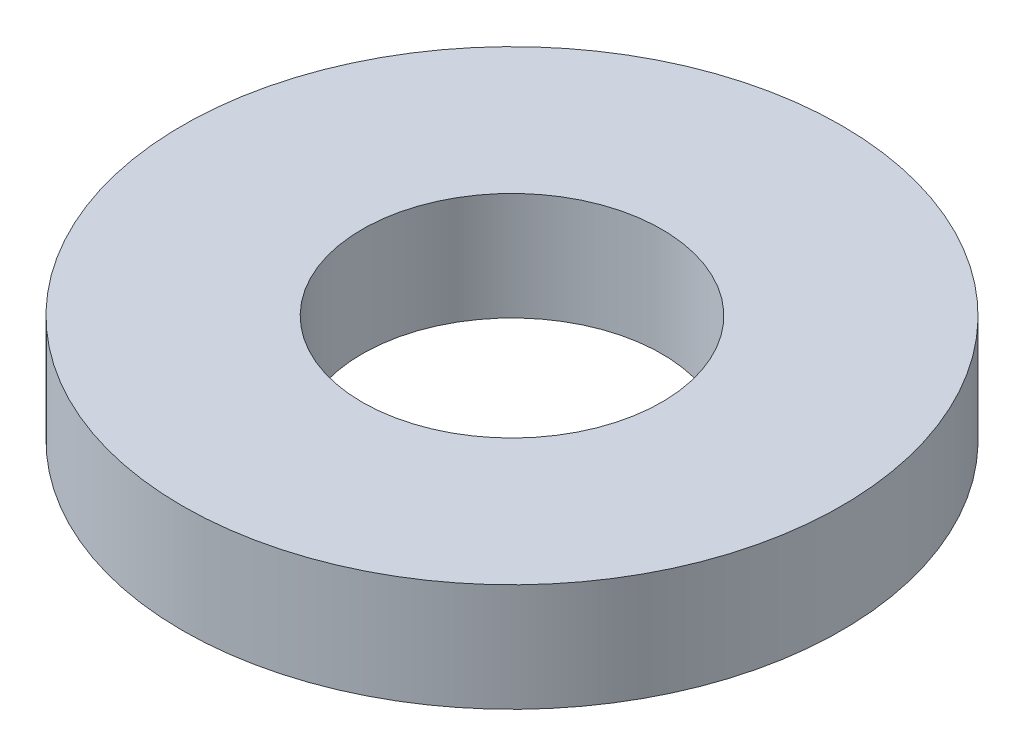
SolidWorks part; units mm, degrees
ref_plane "Front Plane" through (0, 0, 0) normal (0, 0, 1) x (1, 0, 0)
ref_plane "Top Plane" through (0, 0, 0) normal (0, 1, 0) x (1, 0, 0)
ref_plane "Right Plane" through (0, 0, 0) normal (1, 0, 0) x (0, 0, -1)
sketch "Sketch1" plane through (0, 0, 0) normal (0, 1, 0) x (1, 0, 0)
  circle A0 centre (0, 0) radius 82.5
  dimension "FLANGE_OD" = 165
extrude "Boss-Extrude1" add sketch "Sketch1" along normal blind 27
sketch "Sketch2" plane through (0, 0, 0) normal (0, 1, 0) x (1, 0, 0)
  circle A0 centre (0, 0) radius 37.5
  dimension "BORE_D" = 75
extrude "Cut-Extrude1" cut sketch "Sketch2" along normal through all
sketch "Sketch3" plane through (0, 27, 0) normal (0, 1, 0) x (1, 0, 0)
  circle A0 centre (0, 0) radius 33.7661 construction
  circle A1 centre (-33.7661, 0) radius 2.8677
  dimension "BOLT_D" = 5.7354
  dimension "BOLT_PCD" = 67.5322
extrude "Cut-Extrude2" cut sketch "Sketch3" against normal blind 22.9349 rebuild error yes
pattern_circular "CirPattern1" count 4 over 360 rebuild error yes
